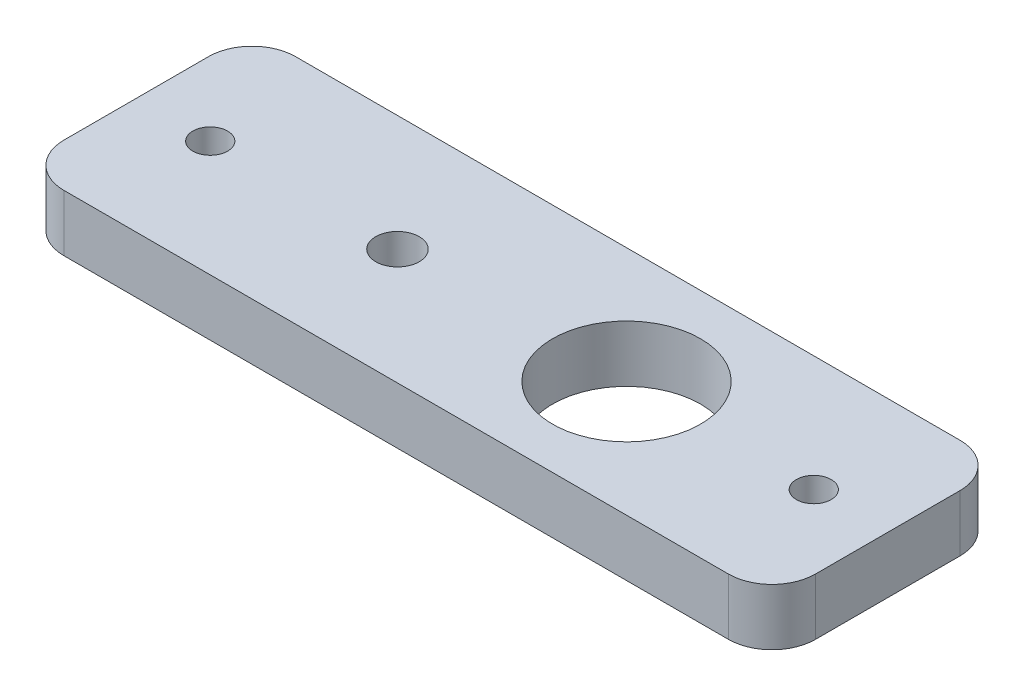
SolidWorks part; units mm, degrees
ref_plane "Front Plane" through (0, 0, 0) normal (0, 0, 1) x (1, 0, 0)
ref_plane "Top Plane" through (0, 0, 0) normal (0, 1, 0) x (1, 0, 0)
ref_plane "Right Plane" through (0, 0, 0) normal (1, 0, 0) x (0, 0, -1)
sketch "Sketch1" plane through (0, 0, 0) normal (0, 1, 0) x (1, 0, 0)
  line L0 (21.5, 0) -> (-47.8, 0) construction
  line L1 (-56.3, 13.3) -> (30, 13.3)
  line L2 (-56.3, 13.3) -> (-56.3, -13.3)
  line L3 (-56.3, -13.3) -> (30, -13.3)
  line L4 (30, 13.3) -> (30, -13.3)
  line L5 (-26.3, 0) -> (0, 0) construction
  circle A0 centre (0, 0) radius 8.3 construction
  circle A1 centre (-47.8, 0) radius 3.5 construction
  circle A2 centre (21.5, 0) radius 3.5 construction
  circle A3 centre (-26.3, 0) radius 8 construction
  circle A4 centre (-26.3, 0) radius 2.5
  circle A5 centre (-47.8, 0) radius 2
  circle A6 centre (21.5, 0) radius 2
  circle A7 centre (0, 0) radius 8.5
  point P11 (-13.15, 0)
  point P12 (-13.15, 0)
  point P13 (-13.15, 13.3)
  point P14 (-56.3, 0)
  dimension "D1" = 10
  dimension "syringe top" = 16.6
  dimension "D2" = 7
  dimension "Motor " = 16
  dimension "D3" = 10
  dimension "D4" = 5
  dimension "D5" = 5
  dimension "D6" = 4
  dimension "D7" = 17
  dimension "D8" = 5
extrude "Boss-Extrude1" add sketch "Sketch1" along normal blind 6.5
fillet "Fillet1" radius 5 4 edges at (-56.3, 3.25, -13.3) (30, 3.25, -13.3) (30, 3.25, 13.3) (-56.3, 3.25, 13.3)
